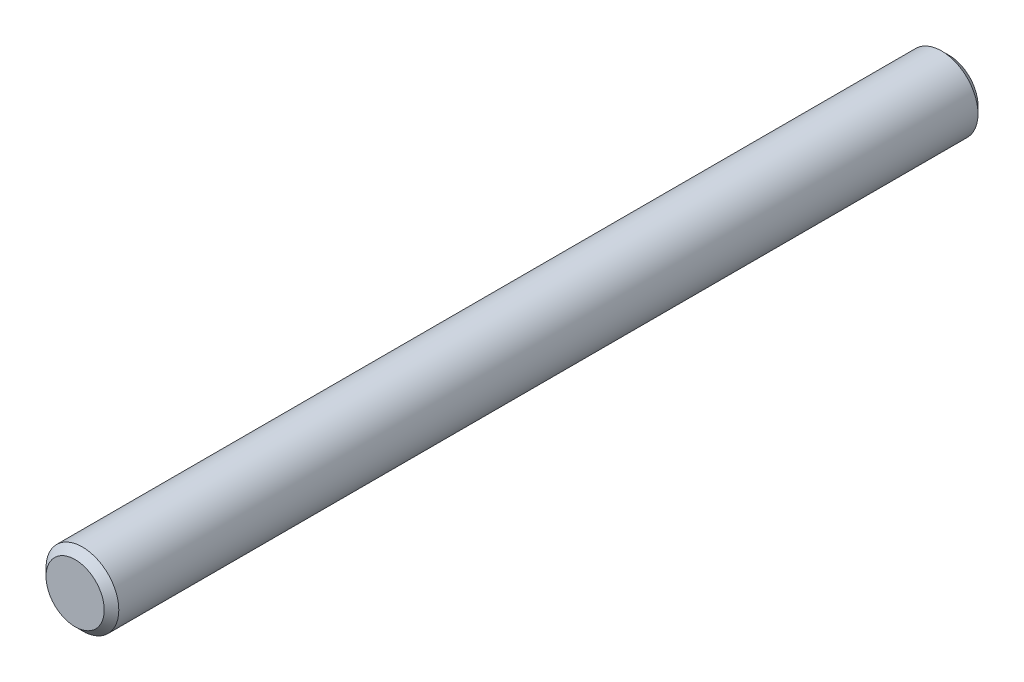
SolidWorks part; units mm, degrees
ref_plane "Front" through (0, 0, 0) normal (0, 0, 1) x (1, 0, 0)
ref_plane "Top" through (0, 0, 0) normal (0, 1, 0) x (1, 0, 0)
ref_plane "Right" through (0, 0, 0) normal (1, 0, 0) x (0, 0, -1)
sketch "Skizze1" plane through (0, 0, 0) normal (0, 0, 1) x (1, 0, 0)
  circle A0 centre (0, 0) radius 2.5
  dimension "D1" = 5
extrude "Aufsatz-Linear austragen1" add sketch "Skizze1" along normal blind 60
chamfer "Fase1" distance 0.5 angle 45 2 edges at (2.5, 0, 0) (2.5, 0, 60)
ref_axis "Axis1" through (0, 0, 59.5) along (0, 0, -1)
